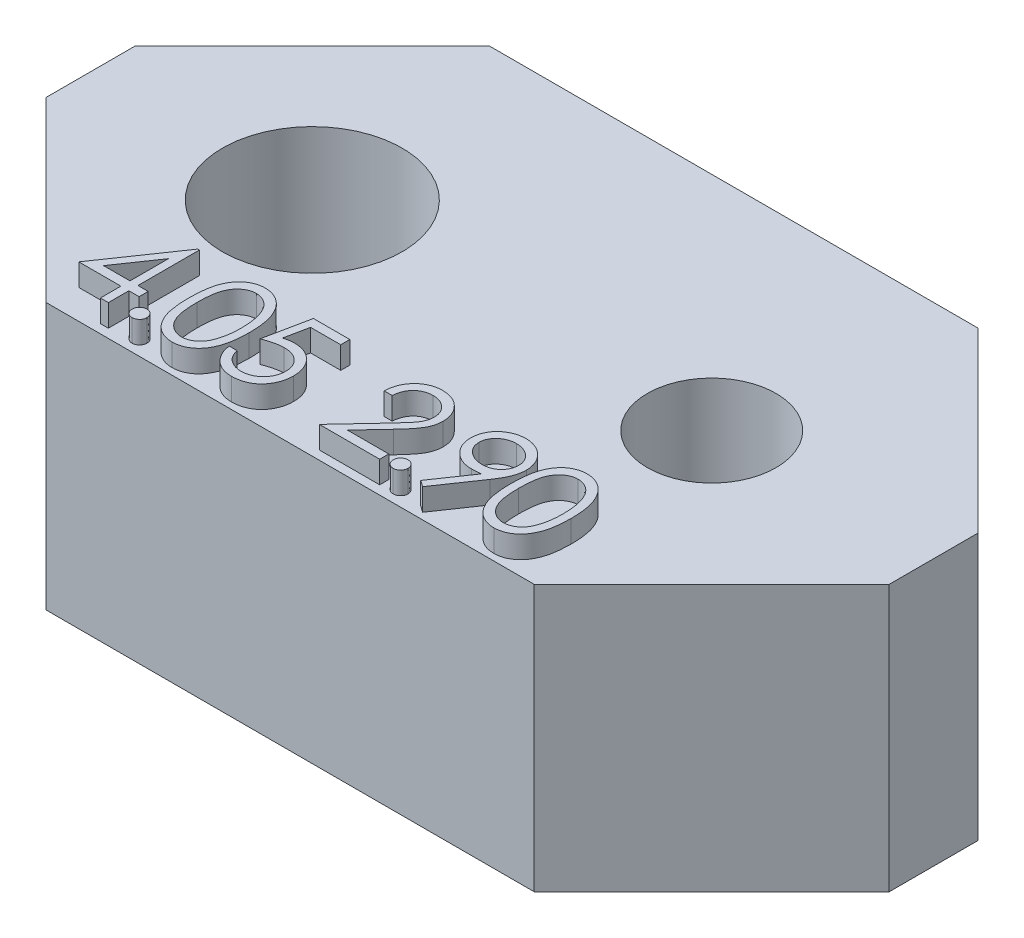
SolidWorks part; units mm, degrees
ref_plane "Спереди" through (0, 0, 0) normal (0, 0, 1) x (1, 0, 0)
ref_plane "Сверху" through (0, 0, 0) normal (0, 1, 0) x (1, 0, 0)
ref_plane "Справа" through (0, 0, 0) normal (1, 0, 0) x (0, 0, -1)
sketch "Эскиз1" plane through (0, 0, 0) normal (0, 1, 0) x (1, 0, 0)
  line L0 (-9.5, 0) -> (9.5, 0) construction
  line L1 (5.5, 5) -> (-5.5, 5)
  line L2 (9.5, 1) -> (9.5, -1)
  line L3 (5.5, -5) -> (-5.5, -5)
  line L4 (-9.5, 1) -> (-9.5, -1)
  line L5 (9.5, 5) -> (-9.5, -5) construction
  line L6 (9.5, -5) -> (-9.5, 5) construction
  line L7 (-5.5, 5) -> (-9.5, 1)
  line L8 (-9.5, -1) -> (-5.5, -5)
  line L9 (9.5, -1) -> (5.5, -5)
  line L10 (5.5, 5) -> (9.5, 1)
  circle A0 centre (-4.5, 0) radius 2.025
  circle A1 centre (4.5, 0) radius 1.45
  point P0 (0, 0)
  dimension "D1" = 4.05
  dimension "D2" = 2.9
  dimension "D3" = 5
  dimension "D4" = 9
  dimension "D5" = 5
  dimension "D6" = 10
  dimension "D7" = 19
extrude "Бобышка-Вытянуть1" add sketch "Эскиз1" along normal blind 6 contours L10 L1 L7 L4 L8 L3 L9 L2 A1 A0 region at (0.2039, 0, 0)
extrude "Бобышка-Вытянуть2" add sketch "Эскиз1<3>" along normal blind 2 contours A0 | A1 region at (-4.5, 0, 0) region at (4.5, 0, 0)
sketch "Эскиз1<3>" plane through (0, 0, 0) normal (0, 1, 0) x (1, 0, 0) same geometry as "Эскиз1"
sketch "Эскиз3" plane through (0, 6, 0) normal (0, 1, 0) x (1, 0, 0)
  line L0 (-5.5, -5) -> (-5.5, -4.8) construction
  line L1 (-5.5, -4.8) -> (5.5, -4.8) construction
  text T0 "4.05  2.90" font "Century Gothic" height 2
  dimension "D1" = 0.2
  dimension "D2" = 11
extrude "Бобышка-Вытянуть3" add sketch "Эскиз3" along normal blind 0.5
